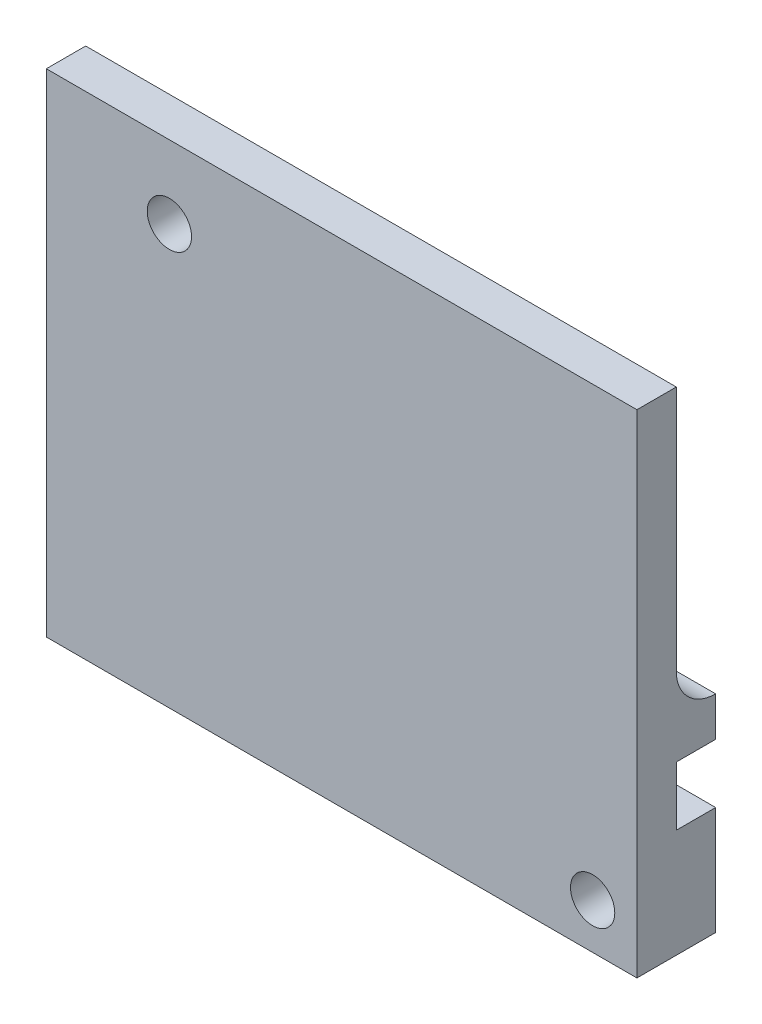
SolidWorks part; units mm, degrees
ref_plane "Płaszczyzna przednia" through (0, 0, 0) normal (0, 0, 1) x (1, 0, 0)
ref_plane "Płaszczyzna górna" through (0, 0, 0) normal (0, 1, 0) x (1, 0, 0)
ref_plane "Płaszczyzna prawa" through (0, 0, 0) normal (1, 0, 0) x (0, 0, -1)
sketch "Sketch1" plane through (0, 0, 0) normal (0, 0, 1) x (1, 0, 0)
  line L1 (0, 0) -> (60, 0)
  line L2 (0, 0) -> (0, 50)
  line L3 (0, 50) -> (60, 50)
  line L4 (60, 0) -> (60, 50)
  line L5 (0, 0) -> (60, 50) construction
  line L6 (0, 50) -> (60, 0) construction
  point P4 (30, 25)
  dimension "D1" = 60
  dimension "D2" = 50
extrude "Boss-Extrude1" add sketch "Sketch1" along normal blind 4
sketch "Sketch2" plane through (0, 0, 0) normal (0, 0, -1) x (-1, 0, 0)
  line L0 (0, 50) -> (0, 0) construction
  line L1 (0, 21) -> (-60, 21)
  line L2 (0, 21) -> (0, 17)
  line L3 (0, 17) -> (-60, 17)
  line L4 (-60, 21) -> (-60, 17)
  line L5 (0, 21) -> (-60, 17) construction
  line L6 (0, 17) -> (-60, 21) construction
  line L7 (-60, 0) -> (-60, 50) construction
  line L9 (0, 0) -> (-60, 0) construction
  point P4 (-30, 19)
  dimension "D1" = 17
  dimension "D2" = 4
extrude "Boss-Extrude2" add sketch "Sketch2" along normal blind 4
fillet "Fillet1" radius 4 1 edges at (30, 21, 0)
sketch "Sketch6" plane through (0, 0, 0) normal (0, 0, -1) x (-1, 0, 0)
  line L0 (0, 0) -> (0, 11)
  line L1 (0, 17) -> (0, 0) construction
  line L2 (-10, 11) -> (0, 11) construction
  line L3 (0, 11) -> (-21, 11)
  line L4 (-27, 5) -> (-27, 0)
  line L5 (0, 0) -> (-60, 0) construction
  line L6 (-27, 0) -> (0, 0)
  line L7 (-33, 5) -> (-33, 0)
  line L8 (-33, 5) -> (-33, -21) construction
  line L9 (-33, 0) -> (-60, 0)
  line L10 (-60, 0) -> (-60, 11)
  line L11 (-60, 0) -> (-60, 17) construction
  line L12 (-60, 11) -> (-39, 11)
  arc A0 (-21, 11) -> (-27, 5) centre (-21, 5) ccw
  arc A1 (-33, 5) -> (-39, 11) centre (-39, 5) ccw
extrude "Boss-Extrude3" add sketch "Sketch6" along normal blind 4
sketch "Sketch3" plane through (0, 0, 4) normal (0, 0, 1) x (1, 0, 0)
  circle A0 centre (12.5, 42.6) radius 2.25
  circle A1 centre (55.5, 4.6) radius 2.25
  dimension "D1" = 4.5
  dimension "D2" = 4.5
extrude "Cut-Extrude1" cut sketch "Sketch3" against normal through all
